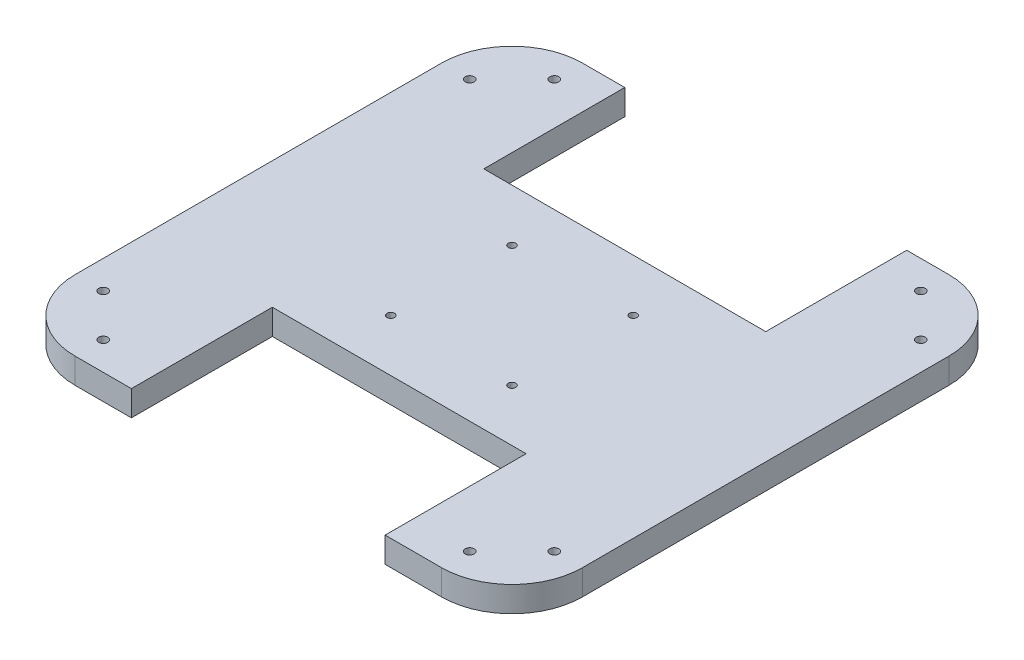
SolidWorks part; units mm, degrees
ref_plane "Front Plane" through (0, 0, 0) normal (0, 0, 1) x (1, 0, 0)
ref_plane "Top Plane" through (0, 0, 0) normal (0, 1, 0) x (1, 0, 0)
ref_plane "Right Plane" through (0, 0, 0) normal (1, 0, 0) x (0, 0, -1)
sketch "Sketch1" plane through (0, 0, 0) normal (0, 1, 0) x (1, 0, 0)
  line L1 (-65, -90) -> (65, -90)
  line L2 (-90, -65) -> (-90, 65)
  line L3 (-65, 90) -> (65, 90)
  line L4 (90, -65) -> (90, 65)
  arc A0 (-90, 65) -> (-65, 90) centre (-65, 65) cw
  arc A1 (65, 90) -> (90, 65) centre (65, 65) cw
  arc A2 (90, -65) -> (65, -90) centre (65, -65) cw
  arc A3 (-65, -90) -> (-90, -65) centre (-65, -65) cw
  point P4 (-90, 0)
  point P6 (0, 90)
  dimension "D3" = 25
  dimension "D1" = 180
  dimension "D2" = 180
extrude "Plate" add sketch "Sketch1" along normal blind 9
sketch "Sketch3" plane through (0, 9, 0) normal (0, 1, 0) x (1, 0, 0)
  line L0 (-65, 90) -> (-65, -90) construction
  line L1 (65, 90) -> (65, -90) construction
  line L2 (-90, 65) -> (90, 65) construction
  line L3 (-90, -65) -> (90, -65) construction
  circle A0 centre (-65, 80) radius 1.6
  circle A1 centre (-80, 65) radius 1.6
  circle A2 centre (80, 65) radius 1.6
  circle A3 centre (80, -65) radius 1.6
  circle A4 centre (65, 80) radius 1.6
  circle A5 centre (65, -80) radius 1.6
  circle A6 centre (-65, -80) radius 1.6
  circle A7 centre (-80, -65) radius 1.6
  dimension "D1" = 3.2
  dimension "D2" = 15
  dimension "D3" = 15
  dimension "D4" = 15
  dimension "D5" = 15
  dimension "D6" = 15
  dimension "D7" = 15
  dimension "D8" = 15
  dimension "D9" = 15
extrude "Hex Holes" cut sketch "Sketch3" against normal through all
sketch "Sketch4" plane through (0, 9, 0) normal (0, 1, 0) x (1, 0, 0)
  line L0 (-90, -65) -> (-90, 65) construction
  line L1 (-65, -90) -> (65, -90) construction
  circle A0 centre (-21.5, 21.5) radius 1.325
  circle A1 centre (21.5, 21.5) radius 1.325
  circle A2 centre (21.5, -21.5) radius 1.325
  circle A3 centre (-21.5, -21.5) radius 1.325
  dimension "D1" = 2.65
  dimension "D2" = 43
  dimension "D3" = 43
  dimension "D4" = 68.5
  dimension "D5" = 68.5
extrude "LiDAR Holes" cut sketch "Sketch4" against normal through all
sketch "Sketch5" plane through (0, 9, 0) normal (0, 1, 0) x (1, 0, 0)
  line L0 (-65, 90) -> (65, 90) construction
  line L1 (50, 90) -> (-50, 90)
  line L2 (50, 90) -> (50, 40)
  line L3 (50, 40) -> (-50, 40)
  line L4 (-50, 90) -> (-50, 40)
  line L5 (-65, -90) -> (65, -90) construction
  line L6 (45, -90) -> (-45, -90)
  line L7 (45, -90) -> (45, -40)
  line L8 (45, -40) -> (-45, -40)
  line L9 (-45, -90) -> (-45, -40)
  point P6 (0, 90)
  point P7 (0, 90)
  point P14 (0, -90)
  point P15 (0, -90)
  dimension "D1" = 100
  dimension "D2" = 50
  dimension "D3" = 50
  dimension "D4" = 90
extrude "Cut-Extrude1" cut sketch "Sketch5" against normal through all
